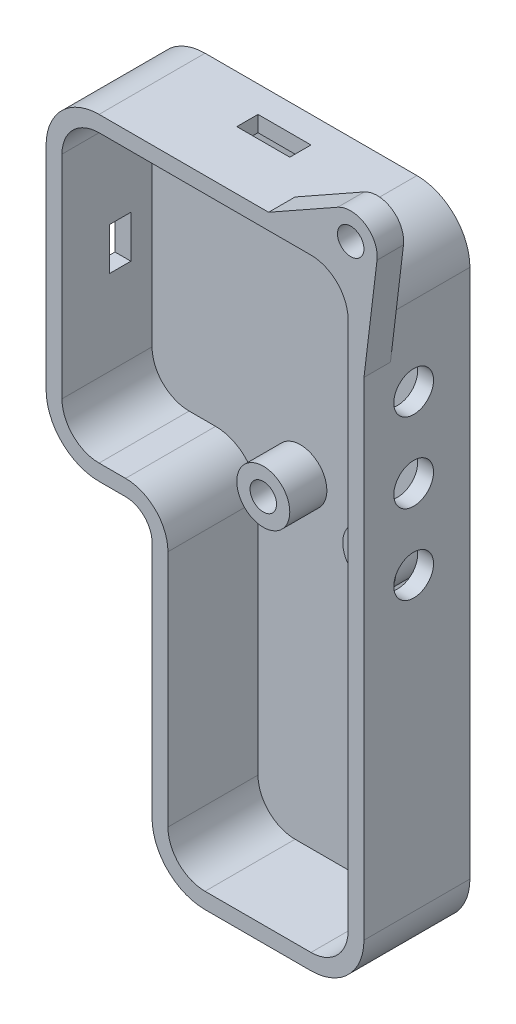
SolidWorks part; units mm, degrees
ref_plane "Alzado" through (0, 0, 0) normal (0, 0, 1) x (1, 0, 0)
ref_plane "Planta" through (0, 0, 0) normal (0, 1, 0) x (1, 0, 0)
ref_plane "Vista lateral" through (0, 0, 0) normal (1, 0, 0) x (0, 0, -1)
sketch "Croquis1" plane through (0, 0, 0) normal (0, 0, 1) x (1, 0, 0)
  line L1 (-80.6068, 54.1736) -> (-40.6068, 54.1736)
  line L2 (-90.6068, 44.1736) -> (-90.6068, 4.1736)
  line L3 (-80.6068, -5.8264) -> (-40.6068, -5.8264)
  line L4 (-30.6068, 44.1736) -> (-30.6068, 4.1736)
  line L5 (-90.6068, 54.1736) -> (-30.6068, -5.8264) construction
  line L6 (-90.6068, -5.8264) -> (-30.6068, 54.1736) construction
  arc A0 (-80.6068, 54.1736) -> (-90.6068, 44.1736) centre (-80.6068, 44.1736) ccw
  arc A1 (-30.6068, 44.1736) -> (-40.6068, 54.1736) centre (-40.6068, 44.1736) ccw
  arc A2 (-30.6068, 4.1736) -> (-40.6068, -5.8264) centre (-40.6068, 4.1736) cw
  arc A3 (-80.6068, -5.8264) -> (-90.6068, 4.1736) centre (-80.6068, 4.1736) cw
  point P0 (-60.6068, 24.1736)
  dimension "D3" = 10
  dimension "D4" = 10
  dimension "D5" = 10
  dimension "D1" = 60
  dimension "D2" = 60
extrude "Saliente-Extruir1" add sketch "Croquis1" along normal blind 50
sketch "Croquis2" plane through (0, -5.8264, 0) normal (0, -1, 0) x (1, 0, 0)
  line L0 (-30.6068, 0) -> (-70.6068, 0)
  line L1 (-70.6068, 0) -> (-70.6068, 50)
  line L2 (-80.6068, 50) -> (-40.6068, 50) construction
  line L3 (-70.6068, 50) -> (-30.6068, 50)
  line L4 (-30.6068, 50) -> (-30.6068, 0) construction
  line L5 (-30.6068, 50) -> (-30.6068, 0)
  dimension "D1" = 40
extrude "Saliente-Extruir2" add sketch "Croquis2" along normal blind 60 and the other way blind 31
fillet "Redondeo1" radius 10 1 edges at (-30.6068, -65.8264, 25) type face fillet first side face at (-30.6068, -10.8264, 25) second side face at (-50.6068, -65.8264, 25)
fillet "Redondeo2" radius 10 1 edges at (-70.6068, -65.8264, 25) type face fillet first side face at (-70.6068, -35.8264, 25) second side face at (-55.6068, -65.8264, 25)
sketch "Croquis3" plane through (-30.6068, 0, 0) normal (1, 0, 0) x (0, 0, -1)
  line L2 (-50, -55.8264) -> (0, -55.8264) construction
  line L3 (-20, -55.8264) -> (-20, 57.2223)
  line L4 (-20, 57.2223) -> (-50, 57.2223)
  line L5 (-50, 57.2223) -> (-50, -55.8264)
  line L6 (-20, -55.8264) -> (-20, -71.3048)
  line L7 (-20, -71.3048) -> (-50, -71.3048)
  line L8 (-50, -71.3048) -> (-50, -55.8264)
  dimension "D1" = 30
extrude "Cortar-Extruir2" cut sketch "Croquis3" against normal blind 76
fillet "Redondeo6" radius 5 1 edges at (-70.6068, -5.8264, 10)
shell "Vaciado2" thickness 3 removed face at (-63.6098, -5.4961, 20)
fillet "Redondeo4" [suppressed] radius 10 type face fillet
sketch "Croquis4" plane through (0, 0, 3) normal (0, 0, 1) x (1, 0, 0)
  line L0 (-78.1068, -2.8264) -> (-33.6068, -2.8264) construction
  line L1 (-80.6068, -2.8264) -> (-75.6068, -2.8264) construction
  line L2 (-33.6068, -55.8264) -> (-33.6068, 44.1736) construction
  circle A0 centre (-39.6068, -2.8264) radius 5
  circle A1 centre (-59.6068, -2.8264) radius 5
  dimension "D1" = 6
  dimension "D2" = 10
  dimension "D3" = 20
extrude "Saliente-Extruir3" add sketch "Croquis4" along normal blind 7
sketch "Croquis5" plane through (0, 0, 10) normal (0, 0, 1) x (1, 0, 0)
  circle A2 centre (-59.6068, -2.8264) radius 2.5
  circle A3 centre (-39.6068, -2.8264) radius 2.5
  dimension "D1" = 5
extrude "Cortar-Extruir3" cut sketch "Croquis5" against normal through all
sketch "Croquis6" plane through (0, 0, 20) normal (0, 0, 1) x (1, 0, 0)
  line L0 (-40.6068, 44.1736) -> (-13.7983, 90.6072) construction
  line L1 (-35.5602, 61.5206) -> (-48.6068, 54.1736)
  line L2 (-80.6068, 54.1736) -> (-40.6068, 54.1736) construction
  line L3 (-30.6068, 36.1736) -> (-28.1429, 56.5641)
  line L4 (-30.6068, -55.8264) -> (-30.6068, 44.1736) construction
  line L5 (-40.6068, 44.1736) -> (-8.3377, 44.1736) construction
  line L6 (-48.6068, 54.1736) -> (-40.6068, 54.1736)
  line L7 (-30.6068, 36.1736) -> (-30.6068, 44.1736)
  circle A0 centre (-33.1068, 57.1639) radius 2.5
  arc A1 (-30.6068, 44.1736) -> (-40.6068, 54.1736) centre (-40.6068, 44.1736) ccw construction
  arc A2 (-28.1429, 56.5641) -> (-35.5602, 61.5206) centre (-33.1068, 57.1639) ccw
  arc A3 (-30.6068, 44.1736) -> (-40.6068, 54.1736) centre (-40.6068, 44.1736) ccw
  dimension "D1" = 5
  dimension "D2" = 10
  dimension "D3" = 15
  dimension "D4" = 8
  dimension "D5" = 8
  dimension "D6" = 60
extrude "Saliente-Extruir4" add sketch "Croquis6" against normal blind 5 contours L1 L6 A3 L7 L3 A2
extrude "Cortar-Extruir4" cut sketch "Croquis6<4>" against normal through all contours A0
sketch "Croquis6<4>" plane through (0, 0, 20) normal (0, 0, 1) x (1, 0, 0) same geometry as "Croquis6"
sketch "Croquis8" plane through (-30.6068, 0, 0) normal (1, 0, 0) x (0, 0, -1)
  line L0 (-15, 54.1736) -> (0, 54.1736) construction
  circle A0 centre (-10.6154, 29.1736) radius 3.75
  circle A1 centre (-10.6154, 14.1736) radius 3.75
  circle A2 centre (-10.6154, -0.8264) radius 3.75
  dimension "D1" = 7.5
  dimension "D2" = 15
  dimension "D3" = 15
  dimension "D4" = 25
extrude "Cortar-Extruir7" cut sketch "Croquis8" against normal up to next
sketch "Croquis9" plane through (-90.6068, 0, 0) normal (-1, 0, 0) x (0, 0, 1)
  line L1 (11, 28.1736) -> (7, 28.1736)
  line L2 (11, 28.1736) -> (11, 20.1736)
  line L3 (11, 20.1736) -> (7, 20.1736)
  line L4 (7, 28.1736) -> (7, 20.1736)
  line L5 (11, 28.1736) -> (7, 20.1736) construction
  line L6 (11, 20.1736) -> (7, 28.1736) construction
  line L7 (0, 24.1736) -> (20, 24.1736) construction
  line L8 (0, 44.1736) -> (0, 4.1736) construction
  line L9 (20, 4.1736) -> (20, 44.1736) construction
  point P0 (9, 24.1736)
  dimension "D1" = 8
  dimension "D2" = 4
  dimension "D3" = 7
extrude "Cortar-Extruir8" cut sketch "Croquis9" against normal up to next
sketch "Croquis10" plane through (0, 54.1736, 0) normal (0, 1, 0) x (1, 0, 0)
  line L0 (-60.6068, 0) -> (-60.6068, -20) construction
  line L1 (-80.6068, -20) -> (-48.6068, -20) construction
  line L3 (-65.6068, -5) -> (-55.6068, -5)
  line L4 (-65.6068, -5) -> (-65.6068, -9)
  line L5 (-65.6068, -9) -> (-55.6068, -9)
  line L6 (-55.6068, -5) -> (-55.6068, -9)
  line L7 (-65.6068, -5) -> (-55.6068, -9) construction
  line L8 (-65.6068, -9) -> (-55.6068, -5) construction
  point P5 (-60.6068, -7)
  dimension "D1" = 7
  dimension "D2" = 4
  dimension "D3" = 10
extrude "Cortar-Extruir9" cut sketch "Croquis10" against normal up to next
